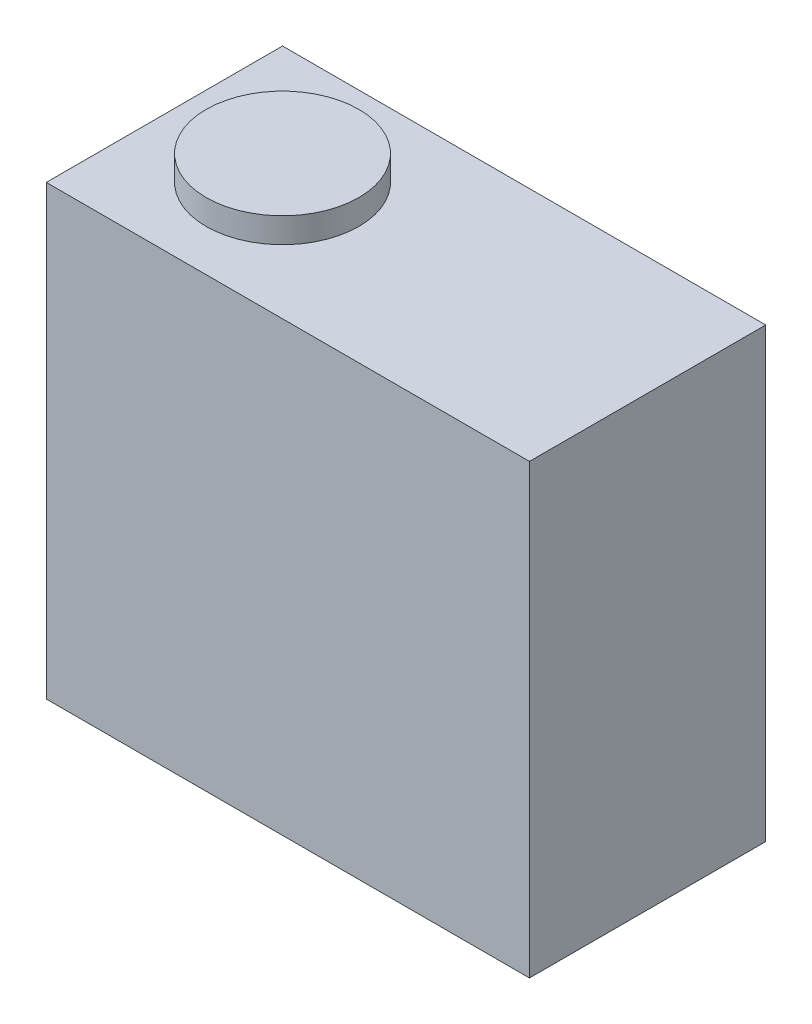
SolidWorks part; units mm, degrees
ref_plane "Front Plane" through (0, 0, 0) normal (0, 0, 1) x (1, 0, 0)
ref_plane "Top Plane" through (0, 0, 0) normal (0, 1, 0) x (1, 0, 0)
ref_plane "Right Plane" through (0, 0, 0) normal (1, 0, 0) x (0, 0, -1)
sketch "Sketch1" plane through (0, 0, 0) normal (0, 1, 0) x (1, 0, 0)
  circle A0 centre (0, 0) radius 6.4
  dimension "D1" = 12.8
extrude "Boss-Extrude1" add sketch "Sketch1" along normal blind 2.1
ref_axis "Axis1" through (0, 15.8722, 0) along (0, -1, 0)
sketch "Sketch2" plane through (0, 0, 0) normal (0, -1, 0) x (1, 0, 0)
  line L0 (0, 0) -> (0, 9.9) construction
  line L1 (0, 0) -> (-9.9, 0) construction
  line L2 (-9.9, 9.9) -> (30.6, 9.9)
  line L3 (-9.9, 9.9) -> (-9.9, -9.9)
  line L4 (-9.9, -9.9) -> (30.6, -9.9)
  line L5 (30.6, 9.9) -> (30.6, -9.9)
  line L6 (0, 0) -> (0, -9.9) construction
  dimension "D1" = 19.8
  dimension "D2" = 40.5
extrude "Boss-Extrude2" add sketch "Sketch2" along normal blind 37.5
